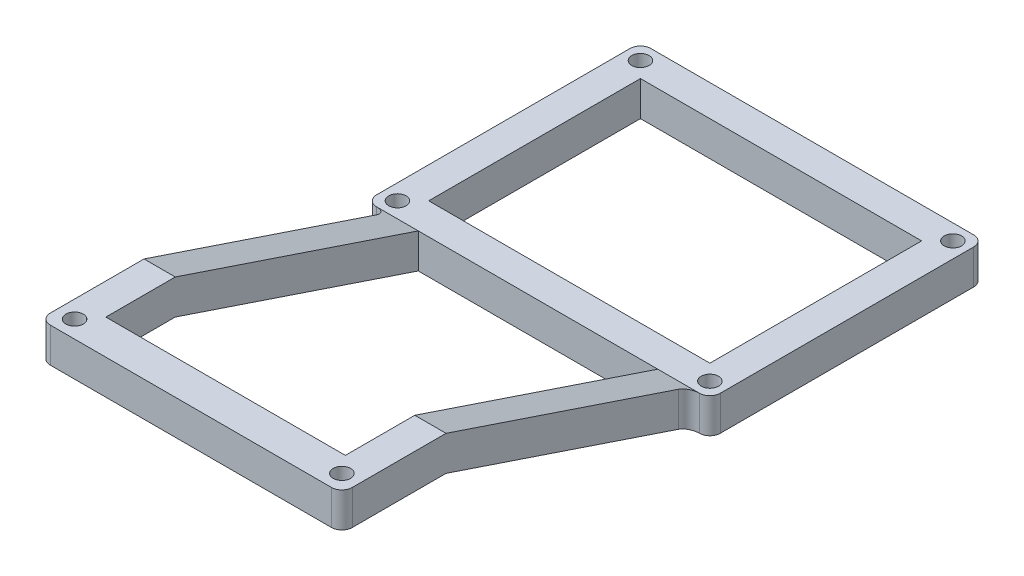
SolidWorks part; units mm, degrees
ref_plane "前视基准面" through (0, 0, 0) normal (0, 0, 1) x (1, 0, 0)
ref_plane "上视基准面" through (0, 0, 0) normal (0, 1, 0) x (1, 0, 0)
ref_plane "右视基准面" through (0, 0, 0) normal (1, 0, 0) x (0, 0, -1)
sketch "草图1" plane through (0, 0, 0) normal (0, 1, 0) x (1, 0, 0)
  line L1 (0, 0) -> (99, 0)
  line L2 (0, 0) -> (0, -79)
  line L3 (0, -79) -> (99, -79)
  line L4 (99, 0) -> (99, -79)
  line L5 (9, -9) -> (90, -9)
  line L6 (9, -9) -> (9, -70)
  line L7 (9, -70) -> (90, -70)
  line L8 (90, -9) -> (90, -70)
  circle A0 centre (94.5, -4.5) radius 2.5
  circle A1 centre (4.5, -4.5) radius 2.5
  circle A2 centre (4.5, -74.5) radius 2.5
  circle A3 centre (94.5, -74.5) radius 2.5
  dimension "D9" = 5
  dimension "D10" = 5
  dimension "D11" = 5
  dimension "D12" = 5
  dimension "D1" = 99
  dimension "D2" = 79
  dimension "D3" = 81
  dimension "D4" = 61
  dimension "D5" = 9
  dimension "D6" = 9
  dimension "D7" = 4.5
  dimension "D8" = 4.5
  dimension "D13" = 4.5
  dimension "D14" = 4.5
extrude "凸台-拉伸1" add sketch "草图1" along normal blind 10
sketch "草图2" plane through (0, 0, 0) normal (0, 0, 1) x (1, 0, 0)
  line L0 (0, 0) -> (0, 70) construction
  line L1 (99, 0) -> (99, 70) construction
  line L2 (0, 70) -> (99, 70) construction
  dimension "D1" = 70
  dimension "D2" = 70
sketch "草图3" plane through (0, 0, 0) normal (1, 0, 0) x (0, 0, -1)
  line L0 (-79, 0) -> (-79, 70) construction
  line L1 (-79, 70) -> (0, 70) construction
  dimension "D1" = 70
ref_plane "基准面4" through (0, 70, 0) normal (0, 1, 0) x (1, 0, 0)
sketch "草图4" plane through (99, 0, 0) normal (1, 0, 0) x (0, 0, -1)
  line L0 (-79, 0) -> (-149, 23.5)
  line L2 (-149, 33.5) -> (-79, 10)
  line L3 (-79, 0) -> (0, 0) construction
  line L5 (-79, 10) -> (-79, 0)
  line L6 (-149, 33.5) -> (-149, 23.5) construction
  line L7 (-149, 33.5) -> (-179, 33.5)
  line L9 (-149, 23.5) -> (-179, 23.5)
  line L10 (-179, 33.5) -> (-179, 23.5)
  dimension "D1" = 33.5
  dimension "D2" = 70
  dimension "D3" = 30
extrude "凸台-拉伸2" add sketch "草图4" against normal blind 15
sketch "草图5" plane through (0, 10, 0) normal (0, 1, 0) x (1, 0, 0)
  line L0 (49.5, 0) -> (49.5, -79) construction
  line L1 (99, 0) -> (0, 0) construction
  line L2 (0, -79) -> (84, -79) construction
sketch "草图6" plane through (0, 0, 0) normal (0, -1, 0) x (1, 0, 0)
  line L0 (49.5, 0) -> (49.5, 79) construction
  line L1 (99, 0) -> (0, 0) construction
  line L2 (0, 79) -> (84, 79) construction
ref_plane "基准面5" through (49.5, 0, 0) normal (-1, 0, 0) x (0, 0, 1)
mirror "镜向1" about plane through (49.5, 0, 0) normal (-1, 0, 0) of "凸台-拉伸2"
extrude "切除-拉伸1" cut sketch "草图4<2>" against normal blind 6
sketch "草图4<2>" plane through (99, 0, 0) normal (1, 0, 0) x (0, 0, -1) same geometry as "草图4"
mirror "镜向2" about plane through (49.5, 0, 0) normal (-1, 0, 0) of "切除-拉伸1"
sketch "草图7" plane through (84, 0, 0) normal (-1, 0, 0) x (0, 0, 1)
  line L0 (149, 33.5) -> (179, 33.5) construction
  line L1 (179, 23.5) -> (169, 23.5)
  line L2 (179, 23.5) -> (179, 33.5)
  line L3 (179, 33.5) -> (169, 33.5)
  line L4 (169, 23.5) -> (169, 33.5)
extrude "凸台-拉伸3" add sketch "草图7" along normal up to next
sketch "草图8" plane through (0, 23.5, 0) normal (0, -1, 0) x (1, 0, 0)
  line L0 (6, 179) -> (93, 179) construction
  line L1 (93, 179) -> (93, 149) construction
  line L2 (6, 179) -> (6, 149) construction
  circle A0 centre (88, 174) radius 2.5
  circle A1 centre (11, 174) radius 2.5
  point P12 (14.1419, 172.547)
  dimension "D1" = 5
  dimension "D2" = 5
  dimension "D4" = 5
  dimension "D3" = 5
  dimension "D5" = 5
  dimension "D6" = 5
extrude "切除-拉伸2" cut sketch "草图8" against normal through all
fillet "圆角1" radius 3 8 edges at (6, 5, 79) (93, 5, 79) (99, 5, 0) (0, 5, 0) (99, 5, 79) (93, 28.5, 179) (0, 5, 79) (6, 28.5, 179)
